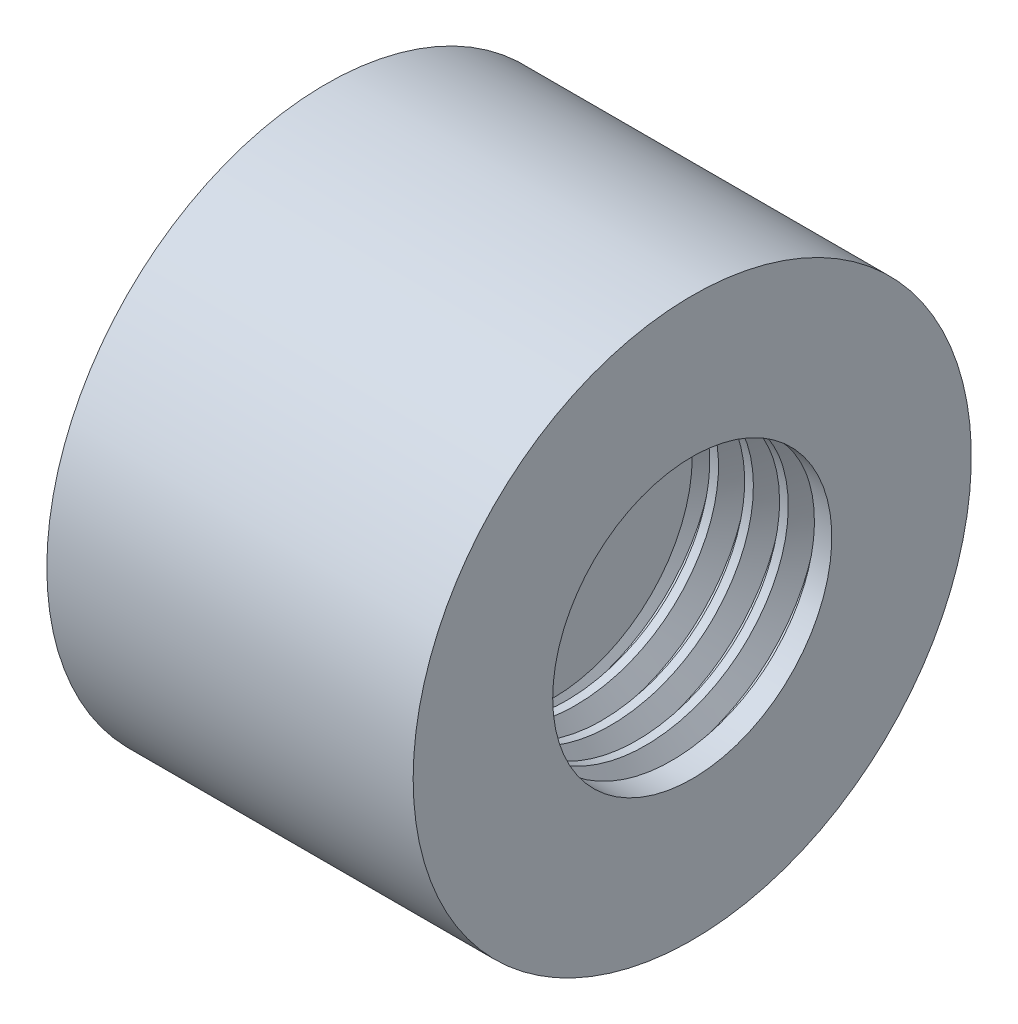
SolidWorks part; units mm, degrees
ref_plane "Ön Düzlem" through (0, 0, 0) normal (0, 0, 1) x (1, 0, 0)
ref_plane "Üst Düzlem" through (0, 0, 0) normal (0, 1, 0) x (1, 0, 0)
ref_plane "Sağ Düzlem" through (0, 0, 0) normal (1, 0, 0) x (0, 0, -1)
sketch "Çizim1" plane through (0, 0, 0) normal (0, 0, 1) x (1, 0, 0)
  line L1 (-6.1502, 1.0862) -> (4.3498, 1.0862)
  line L2 (-6.1502, 1.0862) -> (-6.1502, -6.9138)
  line L3 (-6.1502, -6.9138) -> (4.3498, -6.9138)
  line L4 (4.3498, 1.0862) -> (4.3498, -6.9138)
  dimension "D1" = 10.5
  dimension "D2" = 8
revolve "Döndür1" add sketch "Çizim1" angle 360 about L1
sketch "Çizim3" plane through (4.3498, 0, 0) normal (1, 0, 0) x (0, 0, -1)
  circle A0 centre (0, 1.0862) radius 4
  circle A1 centre (0, 1.0862) radius 8 construction
  dimension "D1" = 0
extrude "Kes-Ekstrüzyon1" cut sketch "Çizim3" against normal blind 4
thread "Diş1" pitch 1 method cut profile "Diş Profili1" start angle 0, offset 0, length 4.5, pitch 1, diameter 8
ref_plane "Düzlem1" through (4.3498, 1.0862, 4) normal (0, -1, 0) x (0, 0, 1)
sketch "Diş Profili1" plane through (4.3498, 1.0862, 4) normal (0, -1, 0) x (0, 0, 1)
  line L0 (0, 0) -> (0, 1) construction
  line L1 (0, 0) -> (0.5413, 0.3125)
  line L2 (0.5413, 0.3125) -> (0.5413, 0.4375)
  line L3 (0.5413, 0.4375) -> (0, 0.75)
  line L4 (0.5413, 0.375) -> (0, 0.375) construction
  line L11 (0, 0) -> (0, 0.75)
  point P2 (0, 0)
  dimension "Pitch" = 1
  dimension "Profile_Angle" = 60
  dimension "Profile_Land" = 0.125
  dimension "Profile_Height" = 0.5413
